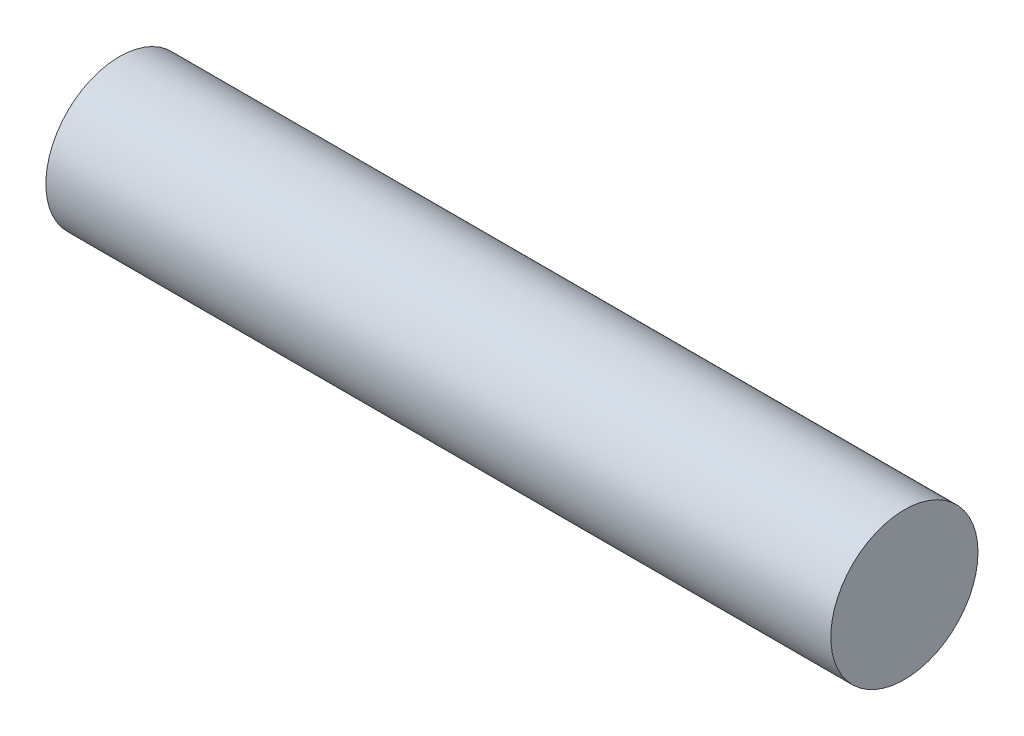
SolidWorks part; units mm, degrees
material "Hexcel AS4C (3000 Filaments)"
ref_plane "X-Y Datum" through (0, 0, 0) normal (0, 0, 1) x (1, 0, 0)
ref_plane "X-Z Datum" through (0, 0, 0) normal (0, 1, 0) x (1, 0, 0)
ref_plane "Y-Z Datum" through (0, 0, 0) normal (1, 0, 0) x (0, 0, -1)
sketch "Sketch1" plane through (0, 0, 0) normal (0, 1, 0) x (1, 0, 0)
  line L0 (139.925, 9.525) -> (139.925, 7.9375)
  line L1 (139.925, 7.9375) -> (19.25, 7.9375)
  line L2 (19.25, 7.9375) -> (19.25, 9.525)
  line L3 (19.25, 9.525) -> (139.925, 9.525)
  line L6 (157.324, 0) -> (-11.2643, 0) construction
  line L7 (19.25, 9.525) -> (19.25, -9.525) construction
  dimension "D1" = 1.5875
revolve "Revolve1" add sketch "Sketch1" angle 360 about L6
sketch "Sketch4" plane through (0, 0, 0) normal (1, 0, 0) x (0, 0, -1)
  line L0 (-9.2357, 0.808) -> (-8.6817, 0.254)
  line L1 (-8.6817, 0.254) -> (-8.6817, -0.254)
  line L2 (-8.6817, -0.254) -> (-9.2357, -0.808)
  line L3 (-8.6817, 0) -> (0, 0) construction
  line L4 (-8.5939, 1.2574) -> (-9.2357, 0.808)
  line L5 (-8.5057, 1.7577) -> (-8.5939, 1.2574)
  line L6 (-8.9551, 2.3995) -> (-8.5057, 1.7577)
  line L7 (-8.245, 2.7306) -> (-8.9551, 2.3995)
  line L8 (-8.0713, 3.208) -> (-8.245, 2.7306)
  line L9 (-8.4024, 3.9181) -> (-8.0713, 3.208)
  line L10 (-7.6456, 4.1209) -> (-8.4024, 3.9181)
  line L11 (-7.3916, 4.5608) -> (-7.6456, 4.1209)
  line L12 (-7.5944, 5.3176) -> (-7.3916, 4.5608)
  line L13 (-6.8138, 5.3859) -> (-7.5944, 5.3176)
  line L14 (-6.4873, 5.7751) -> (-6.8138, 5.3859)
  line L15 (-6.5556, 6.5556) -> (-6.4873, 5.7751)
  line L16 (-5.7751, 6.4873) -> (-6.5556, 6.5556)
  line L17 (-5.3859, 6.8138) -> (-5.7751, 6.4873)
  line L18 (-5.3176, 7.5944) -> (-5.3859, 6.8138)
  line L19 (-4.5608, 7.3916) -> (-5.3176, 7.5944)
  line L20 (-4.1209, 7.6456) -> (-4.5608, 7.3916)
  line L21 (-3.9181, 8.4024) -> (-4.1209, 7.6456)
  line L22 (-3.208, 8.0713) -> (-3.9181, 8.4024)
  line L23 (-2.7306, 8.245) -> (-3.208, 8.0713)
  line L24 (-2.3995, 8.9551) -> (-2.7306, 8.245)
  line L25 (-1.7577, 8.5057) -> (-2.3995, 8.9551)
  line L26 (-1.2574, 8.5939) -> (-1.7577, 8.5057)
  line L27 (-0.808, 9.2357) -> (-1.2574, 8.5939)
  line L28 (-0.254, 8.6817) -> (-0.808, 9.2357)
  line L29 (0.254, 8.6817) -> (-0.254, 8.6817)
  line L30 (0.808, 9.2357) -> (0.254, 8.6817)
  line L31 (1.2574, 8.5939) -> (0.808, 9.2357)
  line L32 (1.7577, 8.5057) -> (1.2574, 8.5939)
  line L33 (2.3995, 8.9551) -> (1.7577, 8.5057)
  line L34 (2.7306, 8.245) -> (2.3995, 8.9551)
  line L35 (3.208, 8.0713) -> (2.7306, 8.245)
  line L36 (3.9181, 8.4024) -> (3.208, 8.0713)
  line L37 (4.1209, 7.6456) -> (3.9181, 8.4024)
  line L38 (4.5608, 7.3916) -> (4.1209, 7.6456)
  line L39 (5.3176, 7.5944) -> (4.5608, 7.3916)
  line L40 (5.3859, 6.8138) -> (5.3176, 7.5944)
  line L41 (5.7751, 6.4873) -> (5.3859, 6.8138)
  line L42 (6.5556, 6.5556) -> (5.7751, 6.4873)
  line L43 (6.4873, 5.7751) -> (6.5556, 6.5556)
  line L44 (6.8138, 5.3859) -> (6.4873, 5.7751)
  line L45 (7.5944, 5.3176) -> (6.8138, 5.3859)
  line L46 (7.3916, 4.5608) -> (7.5944, 5.3176)
  line L47 (7.6456, 4.1209) -> (7.3916, 4.5608)
  line L48 (8.4024, 3.9181) -> (7.6456, 4.1209)
  line L49 (8.0713, 3.208) -> (8.4024, 3.9181)
  line L50 (8.245, 2.7306) -> (8.0713, 3.208)
  line L51 (8.9551, 2.3995) -> (8.245, 2.7306)
  line L52 (8.5057, 1.7577) -> (8.9551, 2.3995)
  line L53 (8.5939, 1.2574) -> (8.5057, 1.7577)
  line L54 (9.2357, 0.808) -> (8.5939, 1.2574)
  line L55 (8.6817, 0.254) -> (9.2357, 0.808)
  line L56 (8.6817, -0.254) -> (8.6817, 0.254)
  line L57 (9.2357, -0.808) -> (8.6817, -0.254)
  line L58 (8.5939, -1.2574) -> (9.2357, -0.808)
  line L59 (8.5057, -1.7577) -> (8.5939, -1.2574)
  line L60 (8.9551, -2.3995) -> (8.5057, -1.7577)
  line L61 (8.245, -2.7306) -> (8.9551, -2.3995)
  line L62 (8.0713, -3.208) -> (8.245, -2.7306)
  line L63 (8.4024, -3.9181) -> (8.0713, -3.208)
  line L64 (7.6456, -4.1209) -> (8.4024, -3.9181)
  line L65 (7.3916, -4.5608) -> (7.6456, -4.1209)
  line L66 (7.5944, -5.3176) -> (7.3916, -4.5608)
  line L67 (6.8138, -5.3859) -> (7.5944, -5.3176)
  line L68 (6.4873, -5.7751) -> (6.8138, -5.3859)
  line L69 (6.5556, -6.5556) -> (6.4873, -5.7751)
  line L70 (5.7751, -6.4873) -> (6.5556, -6.5556)
  line L71 (5.3859, -6.8138) -> (5.7751, -6.4873)
  line L72 (5.3176, -7.5944) -> (5.3859, -6.8138)
  line L73 (4.5608, -7.3916) -> (5.3176, -7.5944)
  line L74 (4.1209, -7.6456) -> (4.5608, -7.3916)
  line L75 (3.9181, -8.4024) -> (4.1209, -7.6456)
  line L76 (3.208, -8.0713) -> (3.9181, -8.4024)
  line L77 (2.7306, -8.245) -> (3.208, -8.0713)
  line L78 (2.3995, -8.9551) -> (2.7306, -8.245)
  line L79 (1.7577, -8.5057) -> (2.3995, -8.9551)
  line L80 (1.2574, -8.5939) -> (1.7577, -8.5057)
  line L81 (0.808, -9.2357) -> (1.2574, -8.5939)
  line L82 (0.254, -8.6817) -> (0.808, -9.2357)
  line L83 (-0.254, -8.6817) -> (0.254, -8.6817)
  line L84 (-0.808, -9.2357) -> (-0.254, -8.6817)
  line L85 (-1.2574, -8.5939) -> (-0.808, -9.2357)
  line L86 (-1.7577, -8.5057) -> (-1.2574, -8.5939)
  line L87 (-2.3995, -8.9551) -> (-1.7577, -8.5057)
  line L88 (-2.7306, -8.245) -> (-2.3995, -8.9551)
  line L89 (-3.208, -8.0713) -> (-2.7306, -8.245)
  line L90 (-3.9181, -8.4024) -> (-3.208, -8.0713)
  line L91 (-4.1209, -7.6456) -> (-3.9181, -8.4024)
  line L92 (-4.5608, -7.3916) -> (-4.1209, -7.6456)
  line L93 (-5.3176, -7.5944) -> (-4.5608, -7.3916)
  line L94 (-5.3859, -6.8138) -> (-5.3176, -7.5944)
  line L95 (-5.7751, -6.4873) -> (-5.3859, -6.8138)
  line L96 (-6.5556, -6.5556) -> (-5.7751, -6.4873)
  line L97 (-6.4873, -5.7751) -> (-6.5556, -6.5556)
  line L98 (-6.8138, -5.3859) -> (-6.4873, -5.7751)
  line L99 (-7.5944, -5.3176) -> (-6.8138, -5.3859)
  line L100 (-7.3916, -4.5608) -> (-7.5944, -5.3176)
  line L101 (-7.6456, -4.1209) -> (-7.3916, -4.5608)
  line L102 (-8.4024, -3.9181) -> (-7.6456, -4.1209)
  line L103 (-8.0713, -3.208) -> (-8.4024, -3.9181)
  line L104 (-8.245, -2.7306) -> (-8.0713, -3.208)
  line L105 (-8.9551, -2.3995) -> (-8.245, -2.7306)
  line L106 (-8.5057, -1.7577) -> (-8.9551, -2.3995)
  line L107 (-8.5939, -1.2574) -> (-8.5057, -1.7577)
  line L108 (-9.2357, -0.808) -> (-8.5939, -1.2574)
  circle A0 centre (0, 0) radius 8.6854 construction
  circle A1 centre (0, 0) radius 9.271 construction
  circle A2 centre (0, 0) radius 12.7
  point P155 (0, 0)
  dimension "D1" = 18.542
  dimension "D2" = 0.508
  dimension "D3" = 17.3708
  dimension "D6" = 25.4
  dimension "D4" = 135
  dimension "D5" = 1.616
  dimension "D7" = 36
sketch "Sketch6" plane through (19.25, 0, 0) normal (-1, 0, 0) x (0, 0, 1)
  circle A0 centre (0, 0) radius 7.9375
  dimension "D1" = 15.875
extrude "Boss-Extrude1" add sketch "Sketch6" against normal blind 101.6
sketch "Sketch7" plane through (120.85, 0, 0) normal (1, 0, 0) x (0, 0, -1)
  circle A0 centre (0, 0) radius 23.308
extrude "Cut-Extrude3" cut sketch "Sketch7" along normal up to surface (19.075 mm away) up to face at (139.925, 0, -9.525)
